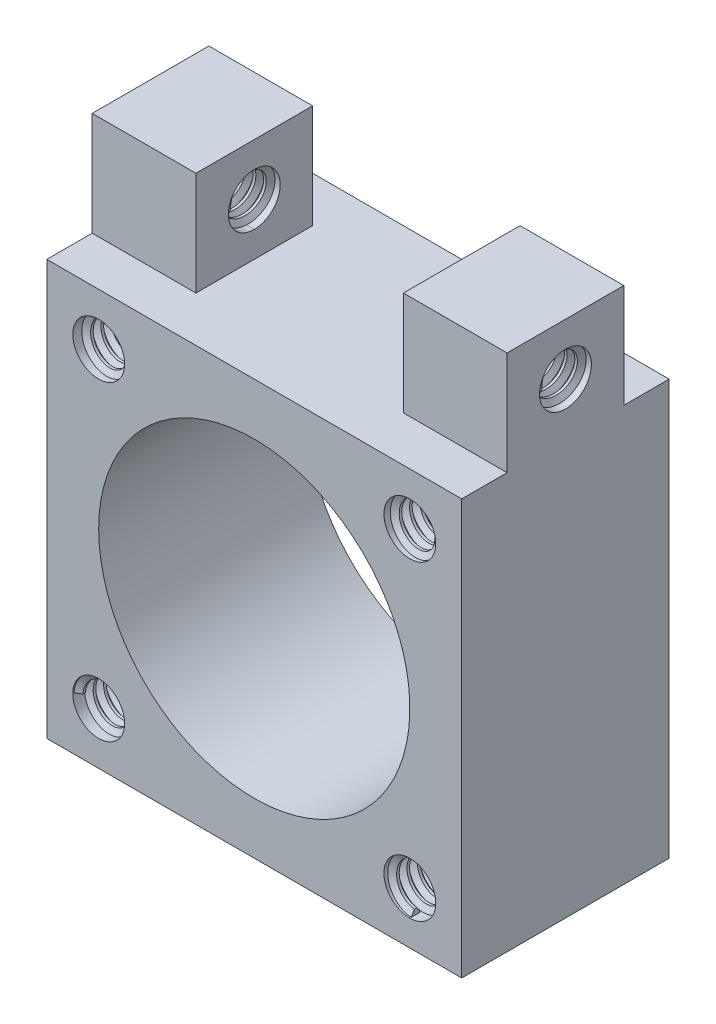
SolidWorks part; units mm, degrees
material "Plain Carbon Steel"
ref_plane "Front Plane" through (0, 0, 0) normal (0, 0, 1) x (1, 0, 0)
ref_plane "Top Plane" through (0, 0, 0) normal (0, 1, 0) x (1, 0, 0)
ref_plane "Right Plane" through (0, 0, 0) normal (1, 0, 0) x (0, 0, -1)
sketch "Sketch1" plane through (0, 0, 0) normal (0, 0, 1) x (1, 0, 0)
  line L0 (0, 65.5134) -> (0, -91.6878) construction
  line L1 (-25.4, 25.4) -> (25.4, 25.4)
  line L2 (-25.4, 25.4) -> (-25.4, -25.4)
  line L3 (-25.4, -25.4) -> (25.4, -25.4)
  line L4 (25.4, 25.4) -> (25.4, -25.4)
  line L5 (77.439, 0) -> (-88.9, 0) construction
  dimension "D1" = 50.8
extrude "Boss-Extrude1" add sketch "Sketch1" along normal blind 25.4
sketch "Sketch2" plane through (0, 0, 0) normal (0, 0, -1) x (-1, 0, 0)
  circle A0 centre (0, 0) radius 19.05
  dimension "D1" = 38.1
extrude "Cut-Extrude1" cut sketch "Sketch2" against normal blind 25.4
ref_plane "Plane1" through (0, 0, 12.7) normal (0, 0, -1) x (-1, 0, 0)
sketch "Sketch3" plane through (-25.4, 0, 0) normal (-1, 0, 0) x (0, 0, 1)
  line L0 (25.4, 25.4) -> (0, 25.4) construction
  line L1 (5.5562, 25.4) -> (19.8438, 25.4)
  line L2 (5.5562, 25.4) -> (5.5562, 38.1)
  line L3 (5.5562, 38.1) -> (19.8437, 38.1)
  line L4 (19.8438, 25.4) -> (19.8437, 38.1)
  line L5 (12.7, 27.94) -> (12.7, -27.94) construction
  line L6 (12.7, 11.6872) -> (12.7, 51.8128) construction
  circle A0 centre (12.7, 31.75) radius 3.175
  dimension "D3" = 6.35
  dimension "D1" = 14.2875
  dimension "D2" = 12.7
  dimension "D4" = 6.35
extrude "Boss-Extrude2" add sketch "Sketch3" against normal blind 12.7
mirror "Mirror1" about plane through (0, 0, 0) normal (1, 0, 0) of "Boss-Extrude2"
sketch "Sketch4" plane through (0, 0, 0) normal (0, 0, -1) x (-1, 0, 0)
  line L0 (-25.4, -25.4) -> (-25.4, 25.4) construction
  line L2 (-25.4, 25.4) -> (25.4, 25.4) construction
  circle A0 centre (-19.05, 19.05) radius 3.175
  circle A1 centre (19.05, 19.05) radius 3.175
  circle A2 centre (19.05, -19.05) radius 3.175
  circle A3 centre (-19.05, -19.05) radius 3.175
  point P15 (0, 0)
  dimension "D1" = 6.35
  dimension "D2" = 6.35
  dimension "D3" = 6.35
  dimension "D4" = 4
extrude "Cut-Extrude2" cut sketch "Sketch4" against normal through all
thread "Thread1" pitch 1.27 method extrude profile "Thread Profile1" start angle 0, offset 0, length 0, pitch 1.27, diameter 6.35
ref_plane "Plane2" through (25.4, 31.75, 15.875) normal (0, -1, 0) x (0, 0, 1)
sketch "Thread Profile1" plane through (25.4, 31.75, 15.875) normal (0, -1, 0) x (0, 0, 1)
  line L0 (0, 0) -> (0, 1.27) construction
  line L11 (0, 0) -> (0, 1.1112)
  line L12 (0, 1.1112) -> (-0.6874, 0.7144)
  line L13 (-0.6874, 0.7144) -> (-0.6874, 0.3969)
  line L15 (-0.6874, 0.3969) -> (0, 0)
  line L17 (-0.6874, 0.5556) -> (0, 0.5556) construction
  point P2 (0, 0)
  dimension "Pitch" = 1.27
  dimension "Profile_Angle" = 60
  dimension "Profile_Land" = 0.3175
  dimension "Profile_Height" = 0.6874
thread "Thread2" pitch 1.27 method extrude profile "Thread Profile2" start angle 0, offset 0, length 0, pitch 1.27, diameter 6.35
ref_plane "Plane3" through (-12.7, 31.75, 15.875) normal (0, -1, 0) x (0, 0, 1)
sketch "Thread Profile2" plane through (-12.7, 31.75, 15.875) normal (0, -1, 0) x (0, 0, 1)
  line L0 (0, 0) -> (0, 1.27) construction
  line L11 (0, 0) -> (0, 1.1112)
  line L12 (0, 1.1112) -> (-0.6874, 0.7144)
  line L13 (-0.6874, 0.7144) -> (-0.6874, 0.3969)
  line L15 (-0.6874, 0.3969) -> (0, 0)
  line L17 (-0.6874, 0.5556) -> (0, 0.5556) construction
  point P2 (0, 0)
  dimension "Pitch" = 1.27
  dimension "Profile_Angle" = 60
  dimension "Profile_Land" = 0.3175
  dimension "Profile_Height" = 0.6874
thread "Thread3" pitch 1.27 method extrude profile "Thread Profile3" start angle 0, offset 0, length 0, pitch 1.27, diameter 6.35
ref_plane "Plane4" through (22.225, 19.05, 0) normal (0, -1, 0) x (1, 0, 0)
sketch "Thread Profile3" plane through (22.225, 19.05, 0) normal (0, -1, 0) x (1, 0, 0)
  line L0 (0, 0) -> (0, 1.27) construction
  line L11 (0, 0) -> (0, 1.1112)
  line L12 (0, 1.1112) -> (-0.6874, 0.7144)
  line L13 (-0.6874, 0.7144) -> (-0.6874, 0.3969)
  line L15 (-0.6874, 0.3969) -> (0, 0)
  line L17 (-0.6874, 0.5556) -> (0, 0.5556) construction
  point P2 (0, 0)
  dimension "Pitch" = 1.27
  dimension "Profile_Angle" = 60
  dimension "Profile_Land" = 0.3175
  dimension "Profile_Height" = 0.6874
pattern_circular "CirPattern1" count 4 over 360 about axis through (0, 0, 0) along (0, 0, -1) of "Thread3"
